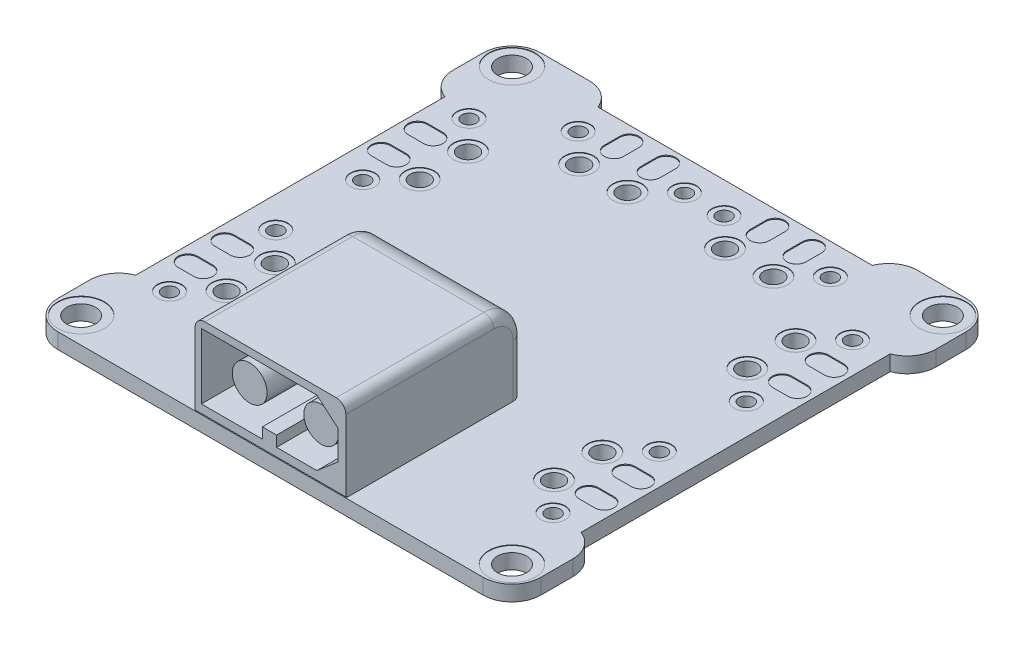
SolidWorks part; units mm, degrees
ref_plane "Front Plane" through (0, 0, 0) normal (0, 0, 1) x (1, 0, 0)
ref_plane "Top Plane" through (0, 0, 0) normal (0, 1, 0) x (1, 0, 0)
ref_plane "Right Plane" through (0, 0, 0) normal (1, 0, 0) x (0, 0, -1)
sketch "Sketch1" plane through (0, 0, 0) normal (0, 1, 0) x (1, 0, 0)
  line L20 (-55, 0) -> (55, 0) construction
  line L22 (-25, -25.1) -> (25, -25.1)
  line L23 (25, -25.1) -> (25, -16)
  line L24 (25, -16) -> (23.05, -16)
  line L25 (23.05, -16) -> (23.05, 16)
  line L26 (23.05, 16) -> (25, 16)
  line L27 (25, 16) -> (25, 24.9)
  line L28 (25, 24.9) -> (14.2, 24.9)
  line L29 (14.2, 24.9) -> (14.2, 23)
  line L30 (14.2, 23) -> (-14.2, 23)
  line L31 (-14.2, 23) -> (-14.2, 24.9)
  line L32 (-14.2, 24.9) -> (-25, 24.9)
  line L33 (-25, 24.9) -> (-25, 16)
  line L34 (-25, 16) -> (-23.05, 16)
  line L35 (-23.05, 16) -> (-23.05, -16)
  line L36 (-23.05, -16) -> (-25, -16)
  line L37 (-25, -16) -> (-25, -25.1)
  line L38 (0, -55) -> (0, 55) construction
  point P0 (0, -25.1)
  point P19 (0, 23)
  point P20 (-83.4325, 47.869)
  point P21 (0, 0)
  point P22 (-83.4325, 21.4541)
  point P23 (72.6325, 25.7062)
  point P24 (72.6325, 16.1711)
  point P25 (72.6325, 22.2272)
  point P26 (18.0394, 12.4343)
  point P27 (23.05, 0)
  dimension "D1" = 50
  dimension "D2" = 10.8
  dimension "D3" = 8.9
  dimension "D4" = 9.1
  dimension "D5" = 50
  dimension "D6" = 48.1
  dimension "D7" = 46.1
extrude "Boss-Extrude1" add sketch "Sketch1" along normal blind 1.6
sketch "Sketch2" plane through (0, 1.6, 0) normal (0, 1, 0) x (1, 0, 0)
  line L0 (-9.45, 21.5) -> (-9.45, 19.9) construction
  line L1 (-8.45, 21.5) -> (-8.45, 19.9)
  line L2 (-10.45, 21.5) -> (-10.45, 19.9)
  line L3 (-5.65, 21.5) -> (-5.65, 19.9) construction
  line L4 (-4.65, 21.5) -> (-4.65, 19.9)
  line L5 (-6.65, 21.5) -> (-6.65, 19.9)
  line L6 (-21.55, 11.7) -> (-19.95, 11.7) construction
  line L7 (-21.55, 12.7) -> (-19.95, 12.7)
  line L8 (-21.55, 10.7) -> (-19.95, 10.7)
  line L9 (-21.55, 7.9) -> (-19.95, 7.9) construction
  line L10 (-21.55, 8.9) -> (-19.95, 8.9)
  line L11 (-21.55, 6.9) -> (-19.95, 6.9)
  line L12 (-21.55, -8.3) -> (-19.95, -8.3) construction
  line L13 (-21.55, -7.3) -> (-19.95, -7.3)
  line L14 (-21.55, -9.3) -> (-19.95, -9.3)
  line L15 (-21.55, -12.1) -> (-19.95, -12.1) construction
  line L16 (-21.55, -11.1) -> (-19.95, -11.1)
  line L17 (-21.55, -13.1) -> (-19.95, -13.1)
  line L18 (-14.2, 24.9) -> (-25, 24.9) construction
  line L19 (-25, 24.9) -> (-25, 16) construction
  line L20 (-25, -25.1) -> (25, -25.1) construction
  line L21 (-23.05, 16) -> (-23.05, -16) construction
  line L22 (14.2, 23) -> (-14.2, 23) construction
  line L23 (0, -0.88) -> (0, 0.88) construction
  line L24 (21.55, -12.1) -> (19.95, -12.1) construction
  line L25 (21.55, -11.1) -> (19.95, -11.1)
  line L26 (21.55, -13.1) -> (19.95, -13.1)
  line L27 (21.55, -8.3) -> (19.95, -8.3) construction
  line L28 (21.55, -7.3) -> (19.95, -7.3)
  line L29 (21.55, -9.3) -> (19.95, -9.3)
  line L30 (21.55, 7.9) -> (19.95, 7.9) construction
  line L31 (21.55, 8.9) -> (19.95, 8.9)
  line L32 (21.55, 6.9) -> (19.95, 6.9)
  line L33 (21.55, 11.7) -> (19.95, 11.7) construction
  line L34 (21.55, 12.7) -> (19.95, 12.7)
  line L35 (21.55, 10.7) -> (19.95, 10.7)
  line L36 (5.65, 21.5) -> (5.65, 19.9) construction
  line L37 (4.65, 21.5) -> (4.65, 19.9)
  line L38 (6.65, 21.5) -> (6.65, 19.9)
  line L39 (9.45, 21.5) -> (9.45, 19.9) construction
  line L40 (8.45, 21.5) -> (8.45, 19.9)
  line L41 (10.45, 21.5) -> (10.45, 19.9)
  circle A0 centre (-22.3, 22.2) radius 1.5
  circle A3 centre (-22.3, -22.4) radius 1.5
  circle A4 centre (-10.05, 16.9) radius 1
  circle A5 centre (-5.05, 16.9) radius 1
  circle A8 centre (-13.05, 19.8) radius 0.75
  circle A9 centre (-2.05, 19.8) radius 0.75
  arc A10 (-8.45, 21.5) -> (-10.45, 21.5) centre (-9.45, 21.5) ccw
  arc A11 (-10.45, 19.9) -> (-8.45, 19.9) centre (-9.45, 19.9) ccw
  arc A12 (-4.65, 21.5) -> (-6.65, 21.5) centre (-5.65, 21.5) ccw
  arc A13 (-6.65, 19.9) -> (-4.65, 19.9) centre (-5.65, 19.9) ccw
  arc A14 (-21.55, 12.7) -> (-21.55, 10.7) centre (-21.55, 11.7) ccw
  arc A15 (-19.95, 10.7) -> (-19.95, 12.7) centre (-19.95, 11.7) ccw
  arc A16 (-21.55, 8.9) -> (-21.55, 6.9) centre (-21.55, 7.9) ccw
  arc A17 (-19.95, 6.9) -> (-19.95, 8.9) centre (-19.95, 7.9) ccw
  arc A18 (-21.55, -7.3) -> (-21.55, -9.3) centre (-21.55, -8.3) ccw
  arc A19 (-19.95, -9.3) -> (-19.95, -7.3) centre (-19.95, -8.3) ccw
  arc A20 (-21.55, -11.1) -> (-21.55, -13.1) centre (-21.55, -12.1) ccw
  arc A21 (-19.95, -13.1) -> (-19.95, -11.1) centre (-19.95, -12.1) ccw
  circle A22 centre (-16.95, 12.3) radius 1
  circle A23 centre (-16.95, 7.3) radius 1
  circle A24 centre (-19.85, 15.3) radius 0.75
  circle A25 centre (-19.85, 4.3) radius 0.75
  circle A26 centre (-19.85, -4.7) radius 0.75
  circle A27 centre (-19.85, -15.7) radius 0.75
  circle A28 centre (-16.95, -7.7) radius 1
  circle A29 centre (-16.95, -12.7) radius 1
  circle A30 centre (16.95, -12.7) radius 1
  circle A31 centre (16.95, -7.7) radius 1
  circle A32 centre (19.85, -15.7) radius 0.75
  circle A33 centre (19.85, -4.7) radius 0.75
  circle A34 centre (19.85, 4.3) radius 0.75
  circle A35 centre (19.85, 15.3) radius 0.75
  circle A36 centre (16.95, 7.3) radius 1
  circle A37 centre (16.95, 12.3) radius 1
  circle A38 centre (2.05, 19.8) radius 0.75
  circle A39 centre (13.05, 19.8) radius 0.75
  circle A40 centre (5.05, 16.9) radius 1
  circle A41 centre (10.05, 16.9) radius 1
  circle A42 centre (22.3, -22.4) radius 1.5
  circle A43 centre (22.3, 22.2) radius 1.5
  arc A44 (21.55, -11.1) -> (21.55, -13.1) centre (21.55, -12.1) cw
  arc A45 (19.95, -13.1) -> (19.95, -11.1) centre (19.95, -12.1) cw
  arc A46 (21.55, -7.3) -> (21.55, -9.3) centre (21.55, -8.3) cw
  arc A47 (19.95, -9.3) -> (19.95, -7.3) centre (19.95, -8.3) cw
  arc A48 (21.55, 8.9) -> (21.55, 6.9) centre (21.55, 7.9) cw
  arc A49 (19.95, 6.9) -> (19.95, 8.9) centre (19.95, 7.9) cw
  arc A50 (21.55, 12.7) -> (21.55, 10.7) centre (21.55, 11.7) cw
  arc A51 (19.95, 10.7) -> (19.95, 12.7) centre (19.95, 11.7) cw
  arc A52 (4.65, 21.5) -> (6.65, 21.5) centre (5.65, 21.5) cw
  arc A53 (6.65, 19.9) -> (4.65, 19.9) centre (5.65, 19.9) cw
  arc A54 (8.45, 21.5) -> (10.45, 21.5) centre (9.45, 21.5) cw
  arc A55 (10.45, 19.9) -> (8.45, 19.9) centre (9.45, 19.9) cw
  point P14 (-9.45, 20.7)
  point P19 (-5.65, 20.7)
  point P26 (-20.75, 11.7)
  point P33 (-20.75, 7.9)
  point P40 (-20.75, -8.3)
  point P47 (-20.75, -12.1)
  point P112 (20.75, -12.1)
  point P119 (20.75, -8.3)
  point P126 (20.75, 7.9)
  point P133 (20.75, 11.7)
  point P140 (5.65, 20.7)
  point P147 (9.45, 20.7)
  point P152 (20.75, 7.9)
  point P153 (21.55, 6.9)
  point P154 (-19.95, 8.9)
  point P155 (-19.95, 7.9)
  point P156 (-19.85, 6.9)
  point P157 (19.85, -7.3)
  dimension "D1" = 3
  dimension "D12" = 1.5
  dimension "D18" = 2
  dimension "D2" = 2.7
  dimension "D3" = 2.7
  dimension "D4" = 2.7
  dimension "D5" = 2
  dimension "D6" = 1.6
  dimension "D7" = 5.8
  dimension "D8" = 5.8
  dimension "D9" = 1.5
  dimension "D10" = 12.2
  dimension "D11" = 32.2
  dimension "D13" = 11
  dimension "D14" = 11
  dimension "D15" = 2.6
  dimension "D16" = 2.6
  dimension "D17" = 3.2
  dimension "D19" = 5
  dimension "D20" = 5
  dimension "D21" = 0.4
  dimension "D22" = 0.4
  dimension "D23" = 6.1
  dimension "D24" = 5.8
  dimension "D25" = 6.1
  dimension "D26" = 1.5
  dimension "D27" = 3.2
  dimension "D28" = 11
  dimension "D29" = 2.6
  dimension "D30" = 5
  dimension "D31" = 0.4
  dimension "D32" = 13
sketch "Sketch3" plane through (0, 1.6, 0) normal (0, 1, 0) x (1, 0, 0)
  circle A1 centre (-2.05, 19.8) radius 0.75
  circle A2 centre (-2.05, 19.8) radius 0.75
  circle A3 centre (-13.05, 19.8) radius 0.75
  circle A4 centre (-13.05, 19.8) radius 0.75
  circle A5 centre (-5.05, 16.9) radius 1
  circle A6 centre (-5.05, 16.9) radius 1
  circle A7 centre (-10.05, 16.9) radius 1
  circle A8 centre (-10.05, 16.9) radius 1
  circle A9 centre (-22.3, -22.4) radius 1.5
  circle A10 centre (-22.3, -22.4) radius 1.5
  circle A11 centre (-22.3, 22.2) radius 1.5
  circle A12 centre (-22.3, 22.2) radius 1.5
  circle A13 centre (-19.85, -4.7) radius 0.75
  circle A34 centre (-19.85, -4.7) radius 0.75
  circle A35 centre (-19.85, 4.3) radius 0.75
  circle A36 centre (-19.85, 4.3) radius 0.75
  circle A37 centre (-19.85, 15.3) radius 0.75
  circle A38 centre (-19.85, 15.3) radius 0.75
  circle A39 centre (-16.95, 7.3) radius 1
  circle A40 centre (-16.95, 7.3) radius 1
  circle A41 centre (-16.95, 12.3) radius 1
  circle A42 centre (-16.95, 12.3) radius 1
  circle A43 centre (-16.95, -12.7) radius 1
  circle A48 centre (-16.95, -12.7) radius 1
  circle A49 centre (-16.95, -7.7) radius 1
  circle A50 centre (-16.95, -7.7) radius 1
  circle A51 centre (-19.85, -15.7) radius 0.75
  circle A52 centre (-19.85, -15.7) radius 0.75
  circle A53 centre (16.95, 7.3) radius 1
  circle A54 centre (16.95, 7.3) radius 1
  circle A55 centre (19.85, 15.3) radius 0.75
  circle A56 centre (19.85, 15.3) radius 0.75
  circle A57 centre (19.85, 4.3) radius 0.75
  circle A58 centre (19.85, 4.3) radius 0.75
  circle A59 centre (19.85, -4.7) radius 0.75
  circle A60 centre (19.85, -4.7) radius 0.75
  circle A61 centre (19.85, -15.7) radius 0.75
  circle A62 centre (19.85, -15.7) radius 0.75
  circle A63 centre (16.95, -7.7) radius 1
  circle A64 centre (16.95, -7.7) radius 1
  circle A65 centre (16.95, -12.7) radius 1
  circle A66 centre (16.95, -12.7) radius 1
  circle A67 centre (22.3, 22.2) radius 1.5
  circle A68 centre (22.3, 22.2) radius 1.5
  circle A69 centre (22.3, -22.4) radius 1.5
  circle A70 centre (22.3, -22.4) radius 1.5
  circle A71 centre (10.05, 16.9) radius 1
  circle A72 centre (10.05, 16.9) radius 1
  circle A73 centre (5.05, 16.9) radius 1
  circle A74 centre (5.05, 16.9) radius 1
  circle A75 centre (13.05, 19.8) radius 0.75
  circle A76 centre (13.05, 19.8) radius 0.75
  circle A77 centre (2.05, 19.8) radius 0.75
  circle A78 centre (2.05, 19.8) radius 0.75
  circle A79 centre (16.95, 12.3) radius 1
  circle A80 centre (16.95, 12.3) radius 1
  dimension "D1" = 0
  dimension "D2" = 0
  dimension "D3" = 0
  dimension "D4" = 0
  dimension "D5" = 0
  dimension "D6" = 0
  dimension "D12" = 0
  dimension "D13" = 0
  dimension "D14" = 0
  dimension "D15" = 0
  dimension "D16" = 0
  dimension "D18" = 0
  dimension "D19" = 0
  dimension "D20" = 0
  dimension "D21" = 0
  dimension "D22" = 0
  dimension "D23" = 0
  dimension "D24" = 0
  dimension "D25" = 0
  dimension "D26" = 0
  dimension "D27" = 0
  dimension "D28" = 0
  dimension "D29" = 0
  dimension "D30" = 0
  dimension "D31" = 0
  dimension "D32" = 0
  dimension "D33" = 0
  dimension "D34" = 0
extrude "Cut-Extrude2" cut sketch "Sketch3" against normal through all
sketch "Sketch4" plane through (0, 1.6, 0) normal (0, 1, 0) x (1, 0, 0)
  line L2 (-4.65, 19.9) -> (-4.65, 21.5)
  line L3 (-6.65, 21.5) -> (-6.65, 19.9)
  line L4 (-4.65, 19.9) -> (-4.65, 21.5)
  line L5 (-6.65, 21.5) -> (-6.65, 19.9)
  line L6 (-10.45, 21.5) -> (-10.45, 19.9)
  line L7 (-8.45, 19.9) -> (-8.45, 21.5)
  line L8 (-10.45, 21.5) -> (-10.45, 19.9)
  line L9 (-8.45, 19.9) -> (-8.45, 21.5)
  line L10 (-19.95, -7.3) -> (-21.55, -7.3)
  line L11 (-21.55, -9.3) -> (-19.95, -9.3)
  line L12 (-19.95, -7.3) -> (-21.55, -7.3)
  line L13 (-21.55, -9.3) -> (-19.95, -9.3)
  line L14 (-19.95, 8.9) -> (-21.55, 8.9)
  line L15 (-21.55, 6.9) -> (-19.95, 6.9)
  line L16 (-19.95, 8.9) -> (-21.55, 8.9)
  line L17 (-21.55, 6.9) -> (-19.95, 6.9)
  line L18 (-19.95, 12.7) -> (-21.55, 12.7)
  line L19 (-21.55, 10.7) -> (-19.95, 10.7)
  line L20 (-19.95, 12.7) -> (-21.55, 12.7)
  line L21 (-21.55, 10.7) -> (-19.95, 10.7)
  line L22 (-19.95, -11.1) -> (-21.55, -11.1)
  line L23 (-21.55, -13.1) -> (-19.95, -13.1)
  line L24 (-19.95, -11.1) -> (-21.55, -11.1)
  line L25 (-21.55, -13.1) -> (-19.95, -13.1)
  line L26 (21.55, -7.3) -> (19.95, -7.3)
  line L27 (19.95, -9.3) -> (21.55, -9.3)
  line L28 (21.55, -7.3) -> (19.95, -7.3)
  line L29 (19.95, -9.3) -> (21.55, -9.3)
  line L30 (21.55, -11.1) -> (19.95, -11.1)
  line L31 (19.95, -13.1) -> (21.55, -13.1)
  line L32 (21.55, -11.1) -> (19.95, -11.1)
  line L33 (19.95, -13.1) -> (21.55, -13.1)
  line L34 (21.55, 12.7) -> (19.95, 12.7)
  line L35 (19.95, 10.7) -> (21.55, 10.7)
  line L36 (21.55, 12.7) -> (19.95, 12.7)
  line L37 (19.95, 10.7) -> (21.55, 10.7)
  line L38 (19.95, 6.9) -> (21.55, 6.9)
  line L39 (21.55, 8.9) -> (19.95, 8.9)
  line L40 (19.95, 6.9) -> (21.55, 6.9)
  line L41 (21.55, 8.9) -> (19.95, 8.9)
  line L42 (8.45, 21.5) -> (8.45, 19.9)
  line L43 (10.45, 19.9) -> (10.45, 21.5)
  line L44 (8.45, 21.5) -> (8.45, 19.9)
  line L45 (10.45, 19.9) -> (10.45, 21.5)
  line L46 (4.65, 21.5) -> (4.65, 19.9)
  line L47 (6.65, 19.9) -> (6.65, 21.5)
  line L48 (4.65, 21.5) -> (4.65, 19.9)
  line L49 (6.65, 19.9) -> (6.65, 21.5)
  circle A1 centre (-2.05, 19.8) radius 0.75
  circle A2 centre (-2.05, 19.8) radius 0.75
  circle A3 centre (-13.05, 19.8) radius 0.75
  circle A4 centre (-13.05, 19.8) radius 0.75
  circle A5 centre (-5.05, 16.9) radius 1
  circle A6 centre (-5.05, 16.9) radius 1
  circle A7 centre (-10.05, 16.9) radius 1
  circle A8 centre (-10.05, 16.9) radius 1
  circle A9 centre (-22.3, -22.4) radius 1.5
  circle A10 centre (-22.3, -22.4) radius 1.5
  circle A11 centre (-22.3, 22.2) radius 1.5
  circle A12 centre (-22.3, 22.2) radius 1.5
  circle A13 centre (-19.85, -4.7) radius 0.75
  arc A14 (-6.65, 19.9) -> (-4.65, 19.9) centre (-5.65, 19.9) ccw
  arc A15 (-4.65, 21.5) -> (-6.65, 21.5) centre (-5.65, 21.5) ccw
  arc A16 (-6.65, 19.9) -> (-4.65, 19.9) centre (-5.65, 19.9) ccw
  arc A17 (-4.65, 21.5) -> (-6.65, 21.5) centre (-5.65, 21.5) ccw
  arc A18 (-10.45, 19.9) -> (-8.45, 19.9) centre (-9.45, 19.9) ccw
  arc A19 (-8.45, 21.5) -> (-10.45, 21.5) centre (-9.45, 21.5) ccw
  arc A20 (-10.45, 19.9) -> (-8.45, 19.9) centre (-9.45, 19.9) ccw
  arc A21 (-8.45, 21.5) -> (-10.45, 21.5) centre (-9.45, 21.5) ccw
  arc A22 (-19.95, -9.3) -> (-19.95, -7.3) centre (-19.95, -8.3) ccw
  arc A23 (-21.55, -7.3) -> (-21.55, -9.3) centre (-21.55, -8.3) ccw
  arc A24 (-19.95, -9.3) -> (-19.95, -7.3) centre (-19.95, -8.3) ccw
  arc A25 (-21.55, -7.3) -> (-21.55, -9.3) centre (-21.55, -8.3) ccw
  arc A26 (-19.95, 6.9) -> (-19.95, 8.9) centre (-19.95, 7.9) ccw
  arc A27 (-21.55, 8.9) -> (-21.55, 6.9) centre (-21.55, 7.9) ccw
  arc A28 (-19.95, 6.9) -> (-19.95, 8.9) centre (-19.95, 7.9) ccw
  arc A29 (-21.55, 8.9) -> (-21.55, 6.9) centre (-21.55, 7.9) ccw
  arc A30 (-19.95, 10.7) -> (-19.95, 12.7) centre (-19.95, 11.7) ccw
  arc A31 (-21.55, 12.7) -> (-21.55, 10.7) centre (-21.55, 11.7) ccw
  arc A32 (-19.95, 10.7) -> (-19.95, 12.7) centre (-19.95, 11.7) ccw
  arc A33 (-21.55, 12.7) -> (-21.55, 10.7) centre (-21.55, 11.7) ccw
  circle A34 centre (-19.85, -4.7) radius 0.75
  circle A35 centre (-19.85, 4.3) radius 0.75
  circle A36 centre (-19.85, 4.3) radius 0.75
  circle A37 centre (-19.85, 15.3) radius 0.75
  circle A38 centre (-19.85, 15.3) radius 0.75
  circle A39 centre (-16.95, 7.3) radius 1
  circle A40 centre (-16.95, 7.3) radius 1
  circle A41 centre (-16.95, 12.3) radius 1
  circle A42 centre (-16.95, 12.3) radius 1
  circle A43 centre (-16.95, -12.7) radius 1
  arc A44 (-19.95, -13.1) -> (-19.95, -11.1) centre (-19.95, -12.1) ccw
  arc A45 (-21.55, -11.1) -> (-21.55, -13.1) centre (-21.55, -12.1) ccw
  arc A46 (-19.95, -13.1) -> (-19.95, -11.1) centre (-19.95, -12.1) ccw
  arc A47 (-21.55, -11.1) -> (-21.55, -13.1) centre (-21.55, -12.1) ccw
  circle A48 centre (-16.95, -12.7) radius 1
  circle A49 centre (-16.95, -7.7) radius 1
  circle A50 centre (-16.95, -7.7) radius 1
  circle A51 centre (-19.85, -15.7) radius 0.75
  circle A52 centre (-19.85, -15.7) radius 0.75
  circle A53 centre (16.95, 7.3) radius 1
  circle A54 centre (16.95, 7.3) radius 1
  circle A55 centre (19.85, 15.3) radius 0.75
  circle A56 centre (19.85, 15.3) radius 0.75
  circle A57 centre (19.85, 4.3) radius 0.75
  circle A58 centre (19.85, 4.3) radius 0.75
  circle A59 centre (19.85, -4.7) radius 0.75
  circle A60 centre (19.85, -4.7) radius 0.75
  circle A61 centre (19.85, -15.7) radius 0.75
  circle A62 centre (19.85, -15.7) radius 0.75
  circle A63 centre (16.95, -7.7) radius 1
  circle A64 centre (16.95, -7.7) radius 1
  circle A65 centre (16.95, -12.7) radius 1
  circle A66 centre (16.95, -12.7) radius 1
  circle A67 centre (22.3, 22.2) radius 1.5
  circle A68 centre (22.3, 22.2) radius 1.5
  circle A69 centre (22.3, -22.4) radius 1.5
  circle A70 centre (22.3, -22.4) radius 1.5
  circle A71 centre (10.05, 16.9) radius 1
  circle A72 centre (10.05, 16.9) radius 1
  circle A73 centre (5.05, 16.9) radius 1
  circle A74 centre (5.05, 16.9) radius 1
  circle A75 centre (13.05, 19.8) radius 0.75
  circle A76 centre (13.05, 19.8) radius 0.75
  circle A77 centre (2.05, 19.8) radius 0.75
  circle A78 centre (2.05, 19.8) radius 0.75
  circle A79 centre (16.95, 12.3) radius 1
  circle A80 centre (16.95, 12.3) radius 1
  arc A82 (19.95, -7.3) -> (19.95, -9.3) centre (19.95, -8.3) ccw
  arc A83 (21.55, -9.3) -> (21.55, -7.3) centre (21.55, -8.3) ccw
  arc A84 (19.95, -7.3) -> (19.95, -9.3) centre (19.95, -8.3) ccw
  arc A85 (21.55, -9.3) -> (21.55, -7.3) centre (21.55, -8.3) ccw
  arc A86 (19.95, -11.1) -> (19.95, -13.1) centre (19.95, -12.1) ccw
  arc A87 (21.55, -13.1) -> (21.55, -11.1) centre (21.55, -12.1) ccw
  arc A88 (19.95, -11.1) -> (19.95, -13.1) centre (19.95, -12.1) ccw
  arc A89 (21.55, -13.1) -> (21.55, -11.1) centre (21.55, -12.1) ccw
  arc A90 (19.95, 12.7) -> (19.95, 10.7) centre (19.95, 11.7) ccw
  arc A91 (21.55, 10.7) -> (21.55, 12.7) centre (21.55, 11.7) ccw
  arc A92 (19.95, 12.7) -> (19.95, 10.7) centre (19.95, 11.7) ccw
  arc A93 (21.55, 10.7) -> (21.55, 12.7) centre (21.55, 11.7) ccw
  arc A94 (19.95, 8.9) -> (19.95, 6.9) centre (19.95, 7.9) ccw
  arc A95 (21.55, 6.9) -> (21.55, 8.9) centre (21.55, 7.9) ccw
  arc A96 (19.95, 8.9) -> (19.95, 6.9) centre (19.95, 7.9) ccw
  arc A97 (21.55, 6.9) -> (21.55, 8.9) centre (21.55, 7.9) ccw
  arc A98 (8.45, 19.9) -> (10.45, 19.9) centre (9.45, 19.9) ccw
  arc A99 (10.45, 21.5) -> (8.45, 21.5) centre (9.45, 21.5) ccw
  arc A100 (8.45, 19.9) -> (10.45, 19.9) centre (9.45, 19.9) ccw
  arc A101 (10.45, 21.5) -> (8.45, 21.5) centre (9.45, 21.5) ccw
  arc A102 (4.65, 19.9) -> (6.65, 19.9) centre (5.65, 19.9) ccw
  arc A103 (6.65, 21.5) -> (4.65, 21.5) centre (5.65, 21.5) ccw
  arc A104 (4.65, 19.9) -> (6.65, 19.9) centre (5.65, 19.9) ccw
  arc A105 (6.65, 21.5) -> (4.65, 21.5) centre (5.65, 21.5) ccw
  dimension "D1" = 0
  dimension "D2" = 0
  dimension "D3" = 0
  dimension "D4" = 0
  dimension "D5" = 0
  dimension "D6" = 0
  dimension "D7" = 0
  dimension "D8" = 0
  dimension "D9" = 0
  dimension "D10" = 0
  dimension "D11" = 0
  dimension "D12" = 0
  dimension "D13" = 0
  dimension "D14" = 0
  dimension "D15" = 0
  dimension "D16" = 0
  dimension "D17" = 0
  dimension "D18" = 0
  dimension "D19" = 0
  dimension "D20" = 0
  dimension "D21" = 0
  dimension "D22" = 0
  dimension "D23" = 0
  dimension "D24" = 0
  dimension "D25" = 0
  dimension "D26" = 0
  dimension "D27" = 0
  dimension "D28" = 0
  dimension "D29" = 0
  dimension "D30" = 0
  dimension "D31" = 0
  dimension "D32" = 0
  dimension "D33" = 0
  dimension "D34" = 0
  dimension "D35" = 0
  dimension "D36" = 0
  dimension "D37" = 0
  dimension "D38" = 0
  dimension "D39" = 0
  dimension "D40" = 0
extrude "Cut-Extrude3" cut sketch "Sketch4" against normal blind 0.1
fillet "Fillet1" radius 3 10 edges at (-25, 0.8, 16) (-25, 0.8, -16) (-14.2, 0.8, -24.9) (25, 0.8, 16) (25, 0.8, -16) (25, 0.8, -24.9) (25, 0.8, 25.1) (-25, 0.8, 25.1) (-25, 0.8, -24.9) (14.2, 0.8, -24.9)
sketch "Sketch5" plane through (0, 1.6, 0) normal (0, 1, 0) x (1, 0, 0)
  line L0 (-22, -25.1) -> (22, -25.1) construction
  line L1 (-7.8, -25.1) -> (7.8, -25.1)
  line L2 (-7.8, -25.1) -> (-7.8, -6.8)
  line L3 (-7.8, -6.8) -> (7.8, -6.8)
  line L4 (7.8, -25.1) -> (7.8, -6.8)
  line L5 (0, -0.88) -> (0, 0.88) construction
  point P6 (0, -6.8)
  dimension "D1" = 15.6
  dimension "D2" = 18.3
extrude "Boss-Extrude2" add sketch "Sketch5" along normal blind 8.5
sketch "Sketch6" plane through (0, 0, 25.1) normal (0, 0, 1) x (1, 0, 0)
  line L0 (-7.15, 9.33) -> (-7.15, 2.56)
  line L1 (-7.15, 2.56) -> (4.8, 2.56)
  line L2 (4.8, 2.56) -> (7, 4.445)
  line L3 (7, 4.445) -> (7, 7.445)
  line L4 (7, 7.445) -> (4.8, 9.33)
  line L5 (4.8, 9.33) -> (-7.15, 9.33)
  line L6 (-7.8, 10.1) -> (7.8, 10.1) construction
  line L7 (7.8, 10.1) -> (7.8, 1.6) construction
  line L8 (27.5, 0) -> (-27.5, 0) construction
  line L9 (-7.8, 10.1) -> (-7.8, 1.6) construction
  point P14 (7, 6.941)
  point P15 (0, 0)
  point P16 (4.8751, 9.33)
  point P17 (7, 7.3832)
  dimension "D1" = 0.77
  dimension "D2" = 0.8
  dimension "D3" = 2.56
  dimension "D4" = 0.65
  dimension "D5" = 3
  dimension "D6" = 3
extrude "Cut-Extrude4" cut sketch "Sketch6" against normal blind 8.7
sketch "Sketch7" plane through (0, 0, 16.4) normal (0, 0, 1) x (1, 0, 0)
  line L0 (-7.15, 9.33) -> (-7.15, 2.56) construction
  line L1 (-7.15, 9.33) -> (-7.15, 2.56) construction
  circle A0 centre (-3.15, 5.945) radius 1.8
  circle A1 centre (4.25, 5.945) radius 1.8
  point P4 (0, 0)
  point P7 (-7.15, 5.945)
  dimension "D1" = 3.6
  dimension "D2" = 7.4
  dimension "D3" = 4
extrude "Boss-Extrude3" add sketch "Sketch7" along normal blind 7.7
fillet "Fillet2" radius 3 1 edges at (0, 10.1, 6.8)
fillet "Fillet3" radius 1 6 edges at (7.8, 4.35, 6.8) (7.8, 9.2213, 7.6787) (-7.8, 4.35, 6.8) (-7.8, 9.2213, 7.6787) (7.8, 10.1, 17.45) (-7.8, 10.1, 17.45)
sketch "Sketch8" plane through (0, 0, 25.1) normal (0, 0, 1) x (1, 0, 0)
  line L0 (7.8, 9.1) -> (7.8, 1.6) construction
  line L1 (-7.8, 1.6) -> (7.8, 1.6)
  line L2 (-7.8, 1.6) -> (-7.8, 1.7)
  line L3 (-7.8, 1.7) -> (7.8, 1.7)
  line L4 (7.8, 1.6) -> (7.8, 1.7)
  dimension "D1" = 0.1
extrude "Cut-Extrude5" cut sketch "Sketch8" against normal blind 0.1
sketch "Sketch9" plane through (0, 2.56, 0) normal (0, 1, 0) x (1, 0, 0)
  line L0 (-7.15, -16.4) -> (4.8, -16.4) construction
  line L1 (-0.84, -16.4) -> (0.63, -16.4)
  line L2 (-0.84, -16.4) -> (-0.84, -25.1)
  line L3 (-0.84, -25.1) -> (0.63, -25.1)
  line L4 (0.63, -16.4) -> (0.63, -25.1)
  line L5 (-7.15, -25.1) -> (4.8, -25.1) construction
  line L6 (-7.8, -25.1) -> (-7.8, -9.8) construction
  dimension "D1" = 1.47
  dimension "D2" = 8.43
extrude "Boss-Extrude4" add sketch "Sketch9" along normal blind 1.1
sketch "Sketch10" plane through (0, 1.6, 0) normal (0, 1, 0) x (1, 0, 0)
  line L0 (0, -5.555) -> (0, 5.555) construction
  circle A5 centre (-22.3, 22.2) radius 2.4
  circle A6 centre (-22.3, 22.2) radius 2.4
  circle A8 centre (2.05, 19.8) radius 1.25
  circle A11 centre (-22.3, -22.4) radius 2.4
  circle A12 centre (-22.3, -22.4) radius 2.4
  circle A14 centre (13.05, 19.8) radius 1.25
  circle A17 centre (-10.05, 16.9) radius 1.5
  circle A18 centre (-10.05, 16.9) radius 1.5
  circle A20 centre (-16.95, 12.3) radius 1.5
  circle A21 centre (-16.95, 12.3) radius 1.5
  circle A23 centre (-16.95, 7.3) radius 1.5
  circle A24 centre (-16.95, 7.3) radius 1.5
  circle A26 centre (-19.85, 15.3) radius 1.25
  circle A27 centre (-19.85, 15.3) radius 1.25
  circle A29 centre (-19.85, 4.3) radius 1.25
  circle A30 centre (-19.85, 4.3) radius 1.25
  circle A32 centre (-16.95, -7.7) radius 1.5
  circle A33 centre (-16.95, -7.7) radius 1.5
  circle A35 centre (-19.85, -4.7) radius 1.25
  circle A36 centre (-19.85, -4.7) radius 1.25
  circle A38 centre (-16.95, -12.7) radius 1.5
  circle A39 centre (-16.95, -12.7) radius 1.5
  circle A41 centre (-19.85, -15.7) radius 1.25
  circle A42 centre (-19.85, -15.7) radius 1.25
  circle A44 centre (-5.05, 16.9) radius 1.5
  circle A45 centre (-5.05, 16.9) radius 1.5
  circle A47 centre (-13.05, 19.8) radius 1.25
  circle A48 centre (-13.05, 19.8) radius 1.25
  circle A49 centre (5.05, 16.9) radius 1.5
  circle A50 centre (-2.05, 19.8) radius 1.25
  circle A51 centre (-2.05, 19.8) radius 1.25
  circle A52 centre (19.85, -15.7) radius 1.25
  circle A53 centre (16.95, -12.7) radius 1.5
  circle A54 centre (19.85, -4.7) radius 1.25
  circle A55 centre (16.95, -7.7) radius 1.5
  circle A56 centre (19.85, 4.3) radius 1.25
  circle A57 centre (19.85, 15.3) radius 1.25
  circle A58 centre (16.95, 7.3) radius 1.5
  circle A59 centre (16.95, 12.3) radius 1.5
  circle A60 centre (10.05, 16.9) radius 1.5
  circle A61 centre (22.3, -22.4) radius 2.4
  circle A62 centre (22.3, 22.2) radius 2.4
  dimension "D1" = 0.9
  dimension "D3" = 0.9
  dimension "D5" = 0.5
  dimension "D6" = 0.5
  dimension "D7" = 0.5
  dimension "D8" = 0.5
  dimension "D9" = 0.5
  dimension "D10" = 0.5
  dimension "D11" = 0.5
  dimension "D12" = 0.5
  dimension "D13" = 0.5
  dimension "D14" = 0.5
  dimension "D15" = 0.5
  dimension "D16" = 0.5
extrude "Cut-Extrude6" cut sketch "Sketch10" against normal blind 0.05
